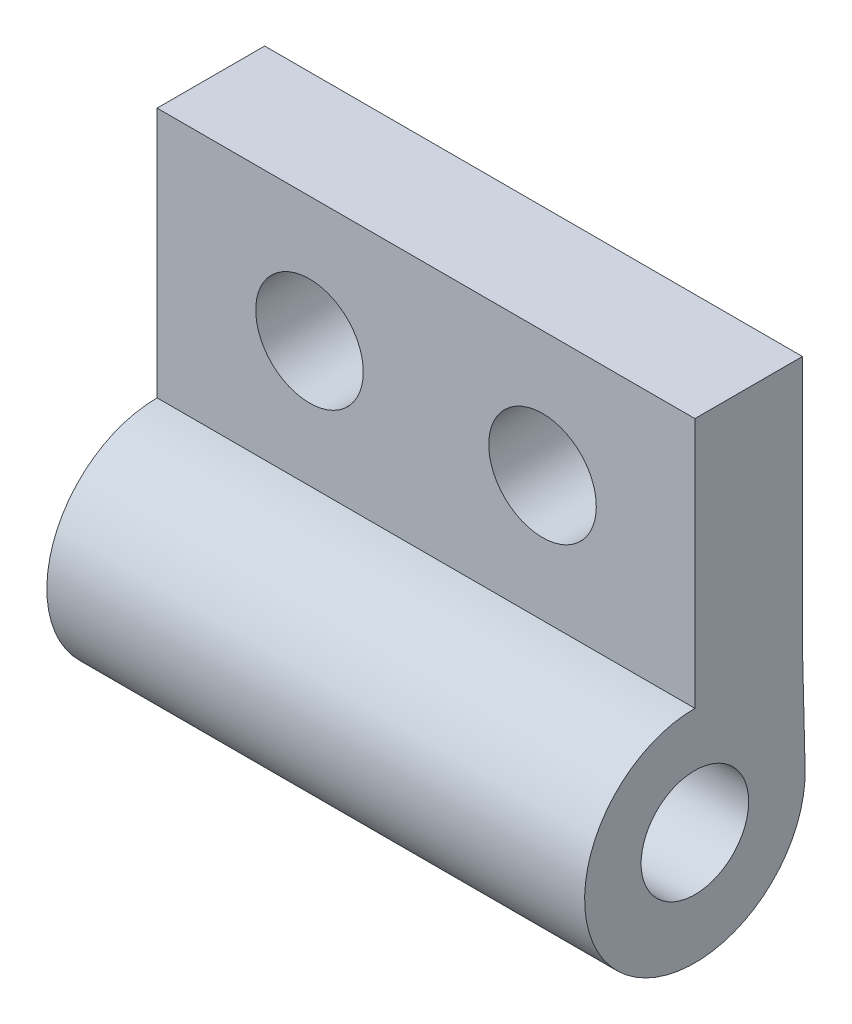
SolidWorks part; units mm, degrees
ref_plane "Płaszczyzna przednia" through (0, 0, 0) normal (0, 0, 1) x (1, 0, 0)
ref_plane "Płaszczyzna górna" through (0, 0, 0) normal (0, 1, 0) x (1, 0, 0)
ref_plane "Płaszczyzna prawa" through (0, 0, 0) normal (1, 0, 0) x (0, 0, -1)
sketch "Szkic1" plane through (0, 0, 0) normal (0, 0, 1) x (1, 0, 0)
  line L1 (-7.5, 3.5) -> (7.5, 3.5)
  line L2 (-7.5, 3.5) -> (-7.5, -3.5)
  line L3 (-7.5, -3.5) -> (7.5, -3.5)
  line L4 (7.5, 3.5) -> (7.5, -3.5)
  line L5 (-7.5, 3.5) -> (7.5, -3.5) construction
  line L6 (-7.5, -3.5) -> (7.5, 3.5) construction
  circle A0 centre (-3.25, 0) radius 1.5
  circle A1 centre (3.25, 0) radius 1.5
  point P4 (0, 0)
  dimension "D1" = 3
  dimension "D2" = 3
  dimension "D3" = 3.25
  dimension "D4" = 3.25
  dimension "D5" = 7
  dimension "D6" = 15
extrude "Dodanie-wyciągnięcie2" add sketch "Szkic1" along normal blind 3
sketch "Szkic2" plane through (7.5, 0, 0) normal (1, 0, 0) x (0, 0, -1)
  line L0 (-3, -3.5) -> (-3, -6.5754) construction
  line L1 (0, -3.5) -> (0.0744, -6.4991)
  line L2 (0, -3.5) -> (-3, -3.5)
  circle A0 centre (-3, -6.5) radius 1.5
  arc A1 (-3, -3.5) -> (0.0744, -6.4991) centre (-3, -6.5754) ccw
  dimension "D2" = 3
  dimension "D1" = 3
extrude "Dodanie-wyciągnięcie3" add sketch "Szkic2" against normal up to surface (15 mm away) up to face at (-7.5, 0, 1.5)
